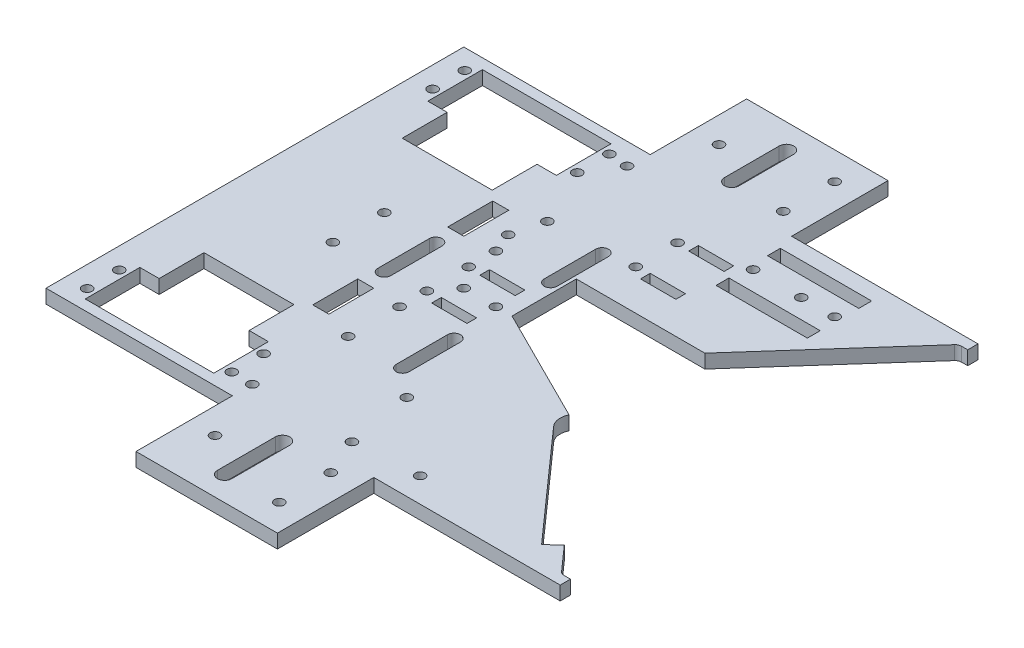
SolidWorks part; units mm, degrees
material "Acrylic (Medium-high impact)"
ref_plane "Front Plane" through (0, 0, 0) normal (0, 0, 1) x (1, 0, 0)
ref_plane "Top Plane" through (0, 0, 0) normal (0, 1, 0) x (1, 0, 0)
ref_plane "Right Plane" through (0, 0, 0) normal (1, 0, 0) x (0, 0, -1)
sketch "Sketch2" plane through (0, 0, 0) normal (0, 1, 0) x (1, 0, 0)
  line L2 (0, 0) -> (0, 65)
  line L3 (0, 65) -> (58, 65)
  line L4 (160, 0) -> (160, 65)
  line L8 (0, 0) -> (160, 0)
  line L9 (102, 65) -> (160, 65)
  line L11 (102, 65) -> (102, 95)
  line L12 (58, 65) -> (58, 95)
  line L13 (58, 95) -> (102, 95)
  dimension "D1" = 65
  dimension "D2" = 160
  dimension "D3" = 44
  dimension "D4" = 30
extrude "Boss-Extrude1" add sketch "Sketch2" along normal blind 4.3
mirror "Mirror1" about plane through (0, 4.3, 0) normal (0, 0, -1) of bodies 101
sketch "Sketch3" plane through (0, 4.3, 0) normal (0, 1, 0) x (1, 0, 0)
  line L0 (160, 61.8) -> (160, -61.8)
  line L1 (120.0126, 20) -> (157.1565, 61.8)
  line L3 (80.0126, 0) -> (80.0126, 20)
  line L4 (80.0126, 20) -> (120.0126, 20)
  line L12 (160, 65) -> (102, 65)
  line L13 (102, 65) -> (102, 95)
  line L15 (102, 95) -> (58, 95)
  line L16 (58, 65) -> (0, 65)
  line L17 (0, 65) -> (0, -65)
  line L18 (0, -65) -> (58, -65)
  line L20 (58, 95) -> (58, 65)
  line L22 (102, -65) -> (160, -65)
  line L23 (160, -65) -> (160, 65)
  line L36 (58, -65) -> (58, -95)
  line L38 (58, -95) -> (102, -95)
  line L39 (58, -95) -> (102, -95)
  line L40 (102, -95) -> (102, -65)
  line L42 (160, -61.8) -> (157.1556, -61.8)
  line L45 (160, 61.8) -> (157.1565, 61.8)
  line L48 (80.0126, 0) -> (120, -20)
  line L49 (120, -20) -> (157.1556, -61.8)
  line M24 (160, -65) -> (160, 65)
  dimension "D2" = 130
  dimension "D3" = 20
  dimension "D4" = 40
  dimension "D1" = 0
extrude "Cut-Extrude1" cut sketch "Sketch3" against normal blind 4.5 contours L48 L49 L1 L4 L3 M24 region at (132.7054, 4.3, -1.1594)
fillet "Fillet1" radius 2 2 edges at (157.1565, 2.15, -61.8) (157.1556, 2.15, 61.8)
ref_axis "Axis1" through (80, 4.3, 95) along (0, 0, -1)
sketch "Sketch4" plane through (0, 4.3, 0) normal (0, 1, 0) x (1, 0, 0)
  line L0 (80, -95) -> (80, 95)
  line L1 (102, -95) -> (58, -95) construction
  line L2 (102, 95) -> (58, 95) construction
ref_plane "Plane2" through (0, 4.3, 0) normal (0, 1, 0) x (1, 0, 0)
sketch "Sketch6" plane through (0, 4.3, 0) normal (0, 1, 0) x (1, 0, 0)
  line L3 (9, -61.8) -> (49, -61.8)
  line L6 (29, -45.8) -> (29, -44.8)
  line L7 (9, -44.8) -> (15, -44.8)
  line L11 (43, -44.8) -> (43, -30.8418)
  line L12 (15, -44.8) -> (15, -30.8418)
  line L13 (15, -30.8418) -> (43, -30.8418)
  line L15 (0, 0) -> (80.0126, 0)
  line L16 (80.0126, 0) -> (120, -20) construction
  line L18 (9, 44.8) -> (15, 44.8)
  line L20 (15, 30.8418) -> (43, 30.8418)
  line L21 (15, 44.8) -> (15, 30.8418)
  line L22 (43, 44.8) -> (43, 30.8418)
  line L25 (15, -45.8) -> (15, -30.8418) construction
  line L27 (9, 61.8) -> (49, 61.8)
  line L30 (4, -61.8) -> (3, -61.8)
  line L31 (0, -61.8) -> (160, -61.8) construction
  line L32 (3, -61.8) -> (4, -61.8)
  line L33 (3, -44.8) -> (3, -62.8) construction
  line L34 (3, -62.8) -> (55, -62.8) construction
  line L35 (55, -44.8) -> (55, -62.8) construction
  line L36 (4, -61.8) -> (54, -61.8) construction
  line L37 (0, 61.8) -> (160, 61.8) construction
  line L38 (54, 61.8) -> (55, 61.8)
  line L39 (54, 61.8) -> (55, 61.8)
  line L40 (43, 44.8) -> (49, 44.8)
  line L41 (4, -45.8) -> (4, -61.8) construction
  line L42 (4, -45.8) -> (54, -45.8) construction
  line L43 (43, -44.8) -> (49, -44.8)
  line L44 (3, -44.8) -> (55, -44.8) construction
  line L45 (29, -45.8) -> (29, -30.8418) construction
  line L46 (43, -45.8) -> (43, -30.8418) construction
  line L47 (54, -45.8) -> (54, -61.8) construction
  line L48 (9, -61.8) -> (49, -61.8)
  line L52 (9, 61.8) -> (9, 44.8)
  line L53 (55, 61.8) -> (54, 61.8)
  line L56 (49, 61.8) -> (49, 44.8)
  line L59 (3, -61.8) -> (4, -61.8)
  line L60 (9, -44.8) -> (9, -61.8)
  line L64 (49, -44.8) -> (49, -61.8)
  dimension "D4" = 1
  dimension "D5" = 14
  dimension "D6" = 14
extrude "Cut-Extrude2" cut sketch "Sketch6" against normal blind 10
sketch "Sketch8" plane through (0, 4.3, 0) normal (0, 1, 0) x (1, 0, 0)
  circle A0 centre (6.5, 58.8) radius 1.5
  circle A1 centre (6.5, 48.8) radius 1.5
  circle A2 centre (51.5, 48.8) radius 1.5
  circle A3 centre (51.5, 58.8) radius 1.5
  circle A4 centre (6.5, -48.7) radius 1.5
  circle A5 centre (6.5, -58.7) radius 1.5
  circle A6 centre (51.5, -58.7) radius 1.5
  circle A7 centre (51.5, -48.8) radius 1.5
  dimension "D7" = 3
extrude "Cut-Extrude3" cut sketch "Sketch8" against normal blind 10
sketch "Sketch9" plane through (0, 0, 0) normal (0, -1, 0) x (1, 0, 0)
  line L0 (75.75, 69.4) -> (75.75, 87.4)
  line L1 (75.75, -87.4) -> (75.75, -70.4)
  line L2 (80.25, -87.4) -> (80.25, -70.4)
  line L4 (80.25, 69.4) -> (80.25, 87.4)
  circle A0 centre (94, 70.4) radius 1.5
  circle A1 centre (66, 78.4) radius 1.5
  circle A2 centre (66, -78.4) radius 1.5
  circle A3 centre (94, -86.4) radius 1.5
  circle A4 centre (94, 86.4) radius 1.5
  circle A5 centre (94, -70.4) radius 1.5
  arc A6 (75.75, -87.4) -> (80.25, -87.4) centre (78, -87.4) ccw
  arc A7 (80.25, -70.4) -> (75.75, -70.4) centre (78, -70.4) ccw
  arc A10 (75.75, 69.4) -> (80.25, 69.4) centre (78, 69.4) ccw
  arc A12 (80.25, 87.4) -> (75.75, 87.4) centre (78, 87.4) ccw
  dimension "D1" = 3
extrude "Cut-Extrude4" cut sketch "Sketch9" against normal blind 10
sketch "Sketch7" plane through (0, 4.3, 0) normal (0, 1, 0) x (1, 0, 0)
  line L0 (0, 0) -> (80.0126, 0)
  line L1 (0, 65) -> (0, -65) construction
  line L2 (80.0126, 0) -> (80.0126, 20) construction
  line L3 (80, -95) -> (80, 95) construction
  line L4 (64, -9) -> (75, -9)
  line L5 (64, -6) -> (75, -6)
  line L6 (64, -9) -> (64, -6)
  line L7 (75, -9) -> (75, -6)
  line L8 (64, -7.5) -> (75, -7.5)
  line L9 (64, 7.5) -> (75, 7.5)
  line L10 (75, 9) -> (75, 6)
  line L11 (64, 9) -> (64, 6)
  line L12 (64, 6) -> (75, 6)
  line L13 (64, 9) -> (75, 9)
  line L14 (89.9874, 30) -> (100.9874, 30)
  line L15 (89.9874, 33) -> (100.9874, 33)
  line L16 (89.9874, 30) -> (89.9874, 33)
  line L17 (100.9874, 30) -> (100.9874, 33)
  line L20 (100.9874, 48) -> (100.9874, 45)
  line L21 (89.9874, 48) -> (89.9874, 45)
  line L22 (89.9874, 45) -> (100.9874, 45)
  line L23 (89.9874, 48) -> (100.9874, 48)
  line L24 (80.0126, 20) -> (120.0126, 20) construction
  circle A0 centre (60.0126, -6.5) radius 1.5
  circle A1 centre (60.0126, 6.5) radius 1.5
  circle A2 centre (86, 32.5) radius 1.5
  circle A3 centre (86, 45.5) radius 1.5
  dimension "D1" = 3
  dimension "D8" = 3
  dimension "D2" = 6.5
  dimension "D3" = 20
  dimension "D6" = 11
  dimension "D4" = 5
  dimension "D5" = 3
  dimension "D7" = 7.5
  dimension "D9" = 11
  dimension "D10" = 3
  dimension "D11" = 12
  dimension "D12" = 13
  dimension "D13" = 10
  dimension "D14" = 3.9874
  dimension "D15" = 0.5
  dimension "D16" = 0.5
  dimension "D17" = 3.9874
  dimension "D18" = 6
  dimension "D19" = 11
sketch "Sketch10" plane through (0, 4.3, 0) normal (0, 1, 0) x (1, 0, 0)
  line L0 (120, -20) -> (156.5589, -61.1287) construction
  line L1 (123.3218, -23.737) -> (149.8964, -53.6334)
  line L2 (116.263, -23.3218) -> (146.1593, -56.9552)
  line L3 (149.8964, -53.6334) -> (146.1593, -56.9552)
  line L4 (120, -20) -> (156.5589, -61.1287) construction
  line L5 (116.263, -23.3218) -> (152.8218, -64.4505) construction
  arc A0 (123.3218, -23.737) -> (116.263, -23.3218) centre (120, -20) ccw
  dimension "D1" = 5
  dimension "D2" = 45
extrude "Cut-Extrude5" cut sketch "Sketch10" against normal blind 10
sketch "Sketch11" plane through (0, 0, 0) normal (0, -1, 0) x (1, 0, 0)
  line L0 (0, 0) -> (80.0126, 0) construction
  line L1 (80, 95) -> (80, -95) construction
  line L2 (80.0126, 0) -> (0, 0)
  line L4 (75, 31.0313) -> (75, 15.0313)
  line L6 (79, 31.0313) -> (79, 15.0313)
  line L7 (79, -31.0313) -> (79, -15.0313)
  line L8 (75, -31.0313) -> (75, -15.0313)
  circle A0 centre (60, 31) radius 1.5
  circle A1 centre (60, 15) radius 1.5
  arc A2 (75, 31.0313) -> (79, 31.0313) centre (77, 31.0313) cw
  arc A3 (75, 15.0313) -> (79, 15.0313) centre (77, 15.0313) ccw
  arc A4 (75, -15.0313) -> (79, -15.0313) centre (77, -15.0313) cw
  arc A5 (75, -31.0313) -> (79, -31.0313) centre (77, -31.0313) ccw
  circle A6 centre (60, -15) radius 1.5
  circle A7 centre (60, -31) radius 1.5
  dimension "D1" = 3
  dimension "D2" = 16
  dimension "D3" = 15
  dimension "D4" = 20
  dimension "D5" = 15
  dimension "D6" = 4
extrude "Cut-Extrude6" cut sketch "Sketch11" against normal blind 10 contours L4 A3 L6 A2 | L8 A5 L7 A4 | A7 | A0 | A1 | A6 region at (77, 0, 23.0313) region at (77, 0, -23.0313) region at (60, 0, -31)
sketch "Sketch12" plane through (0, 0, 0) normal (0, -1, 0) x (-1, 0, 0)
  line L0 (0, 0) -> (-80.0126, 0) construction
  line L3 (-50.2627, -8) -> (-50.2627, 8)
  line L4 (-50.2627, 0) -> (-46.2627, 0)
  line L5 (-46.2627, -8) -> (-46.2627, 8)
  line L6 (0, 0) -> (-46.2627, 0)
  line L7 (0, 65) -> (0, -65) construction
  line L8 (-160, -61.8) -> (0, -61.8) construction
  line L9 (-80.0126, 0) -> (-50.2627, 0)
  line L10 (-80.0126, 0) -> (-115.5281, -17.7634) construction
  line L11 (-80.0126, 0) -> (-80.0126, 20) construction
  line L12 (-58, -65) -> (0, -65) construction
  line L13 (-58, 65) -> (0, 65) construction
  circle A0 centre (-32.2627, -8) radius 1.5
  circle A1 centre (-32.2627, 8) radius 1.5
  arc A2 (-46.2627, 8) -> (-50.2627, 8) centre (-48.2627, 8) ccw
  arc A3 (-50.2627, -8) -> (-46.2627, -8) centre (-48.2627, -8) ccw
  circle A5 centre (-32.2627, -8) radius 1.5 construction
  circle A6 centre (-32.2627, 8) radius 1.5 construction
  dimension "D1" = 3
  dimension "D8" = 8
  dimension "D9" = 8
  dimension "D2" = 8
  dimension "D3" = 14
  dimension "D4" = 4
  dimension "D5" = 61.8
  dimension "D6" = 65
  dimension "D7" = 65
extrude "Cut-Extrude7" cut sketch "Sketch12" against normal blind 10 contours A3 L5 L4 L3 | L4 L5 A2 L3 | A0 | A1 region at (48.2627, 0, 4.7958) region at (48.2627, 0, -4.7958) region at (32.2627, 0, 8) region at (32.2627, 0, -8)
extrude "Cut-Extrude8" cut sketch "Sketch7" against normal blind 9 contours A0 | L4 L7 L5 L6 | L12 L10 L13 L11 | A1 | L23 L20 L22 L21 | L15 L17 L14 L16 | A3 | A2
sketch "Sketch13" plane through (0, 4.3, 0) normal (0, 1, 0) x (1, 0, 0)
  line L0 (80.0126, 0) -> (59.0194, 0)
  line L1 (80, -95) -> (80, 95) construction
  circle A0 centre (65, 0) radius 1.5
  circle A1 centre (75, 0) radius 1.5
  dimension "D2" = 3
  dimension "D3" = 5
  dimension "D1" = 10
extrude "Cut-Extrude9" cut sketch "Sketch13" against normal blind 10 contours L0 A0 | L0 A0 | L0 A1 | L0 A1 region at (75, 4.3, 0.6366) region at (75, 4.3, -0.6366) region at (65, 4.3, 0.6366) region at (65, 4.3, -0.6366)
sketch "Sketch14" plane through (0, 4.3, 0) normal (0, 1, 0) x (1, 0, 0)
  circle A0 centre (57.5, 58.3) radius 1.5
  circle A2 centre (57.5, 21.3) radius 1.5
  circle A3 centre (85.5653, -38.3098) radius 1.5
  circle A4 centre (108.7541, -57.3434) radius 1.5
  dimension "D1" = 3
  dimension "D2" = 3
extrude "Cut-Extrude10" cut sketch "Sketch14" against normal blind 10
sketch "Sketch15" plane through (0, 4.3, 0) normal (0, 1, 0) x (1, 0, 0)
  line L1 (46, 28) -> (51, 28)
  line L2 (46, 28) -> (46, 14)
  line L3 (46, 14) -> (51, 14)
  line L4 (51, 28) -> (51, 14)
  line L6 (0, 65) -> (0, -65) construction
  line L7 (80.0126, 0) -> (53.7017, 0)
  line L8 (46, -14) -> (51, -14)
  line L9 (51, -28) -> (51, -14)
  line L10 (46, -28) -> (51, -28)
  line L11 (46, -28) -> (46, -14)
  arc A0 (50.2627, 8) -> (46.2627, 8) centre (48.2627, 8) ccw construction
  arc A1 (46.2627, -8) -> (50.2627, -8) centre (48.2627, -8) ccw construction
  dimension "D1" = 46
  dimension "D2" = 5
  dimension "D3" = 14
  dimension "D4" = 14
  dimension "D5" = 14
  dimension "D6" = 6
  dimension "D7" = 6
extrude "Cut-Extrude11" cut sketch "Sketch15" against normal blind 10 contours L4 L1 L2 L3 | L11 L10 L9 L8 region at (48.5, 4.3, -21) region at (48.5, 4.3, 21)
sketch "Sketch16" plane through (0, 4.3, 0) normal (0, 1, 0) x (1, 0, 0)
  circle A0 centre (89, -58.8) radius 1.5
  circle A1 centre (58, -58.8) radius 1.5
  dimension "D1" = 3
extrude "Cut-Extrude12" cut sketch "Sketch16" against normal blind 10
ref_plane "Plane3" through (44.2426, 0, 0) normal (1, 0, 0) x (0, 0, -1)
sketch "Sketch17" plane through (44.2426, 0, 0) normal (1, 0, 0) x (0, 0, -1)
  line L4 (0, 0) -> (20, 0)
  line L5 (20, 0) -> (20, 4.3)
  line L6 (20, 4.3) -> (0, 4.3)
  line L7 (0, 4.3) -> (0, 0)
  line L8 (0, 0) -> (20, 0)
  line L9 (20, 0) -> (20, 4.3)
  line L10 (20, 4.3) -> (0, 4.3)
  line L11 (0, 4.3) -> (0, 0)
  circle A0 centre (-2.83, 16.28) radius 0.5
  point P6 (0, 2.15)
  dimension "D4" = 1
  dimension "D2" = 2.83
  dimension "D3" = 14.13
  dimension "D1" = 0
sketch "Sketch18" plane through (0, 4.3, 0) normal (0, 1, 0) x (1, 0, 0)
  line L0 (121.5, 50) -> (128.9, 50)
  line L1 (103.5, 60) -> (131.9, 60)
  line L2 (102, 65) -> (102, 95) construction
  line L3 (160, 65) -> (102, 65) construction
  line L4 (103.5, 60) -> (103.5, 56)
  line L5 (106.5, 50) -> (118.5, 50)
  line L6 (131.9, 60) -> (131.9, 56)
  line L7 (103.5, 60) -> (131.9, 60)
  line L8 (103.5, 60) -> (103.5, 56)
  line L9 (103.5, 56) -> (131.9, 56)
  line L10 (131.9, 60) -> (131.9, 56)
  line L11 (103.5, 44) -> (131.9, 44)
  line L12 (131.9, 40) -> (131.9, 44)
  line L13 (103.5, 40) -> (131.9, 40)
  line L14 (103.5, 40) -> (103.5, 44)
  circle A0 centre (105, 50) radius 1.5
  circle A1 centre (120, 50) radius 1.5
  circle A3 centre (130.4, 50) radius 1.5
  dimension "D1" = 3
  dimension "D6" = 3
  dimension "D2" = 15
  dimension "D4" = 3
  dimension "D5" = 15
  dimension "D7" = 25.4
  dimension "D8" = 4
  dimension "D9" = 6
extrude "Cut-Extrude13" cut sketch "Sketch18" against normal blind 10 contours L4 L9 L6 L1 | A0 | A1 | A3 | L14 L13 L12 L11 region at (130.4, 4.3, -50) region at (120, 4.3, -50) region at (105, 4.3, -50) region at (117.7, 4.3, -58) region at (117.7, 4.3, -42)
